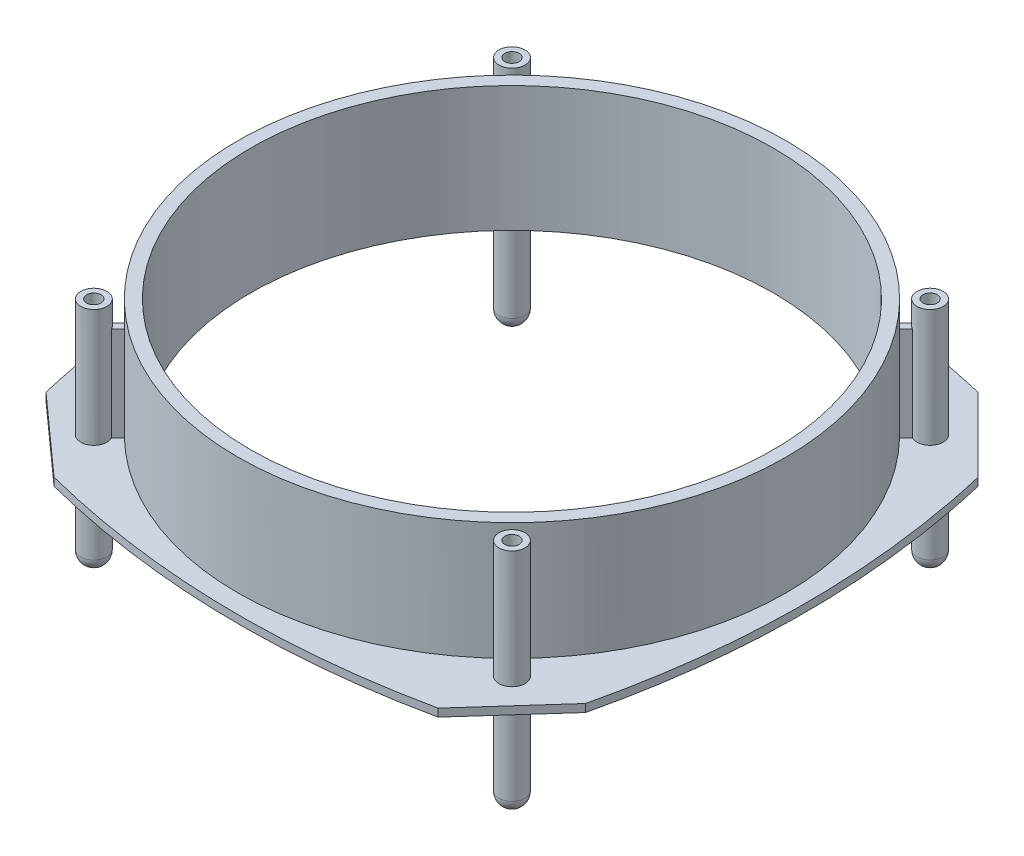
SolidWorks part; units mm, degrees
ref_plane "Front Plane" through (0, 0, 0) normal (0, 0, 1) x (1, 0, 0)
ref_plane "Top Plane" through (0, 0, 0) normal (0, 1, 0) x (1, 0, 0)
ref_plane "Right Plane" through (0, 0, 0) normal (1, 0, 0) x (0, 0, -1)
sketch "Sketch2" plane through (0, 0, 0) normal (0, 1, 0) x (1, 0, 0)
  line L0 (3824.4294, -5236.7276) -> (5157.6927, -3749.6242)
  line L2 (5163.9685, 3752.3444) -> (3751.2089, 5164.1439)
  line L4 (-3751.7702, 5163.5828) -> (-5163.7079, 3750.9614)
  line L6 (-5163.0762, -3751.9198) -> (-3675.9728, -5085.183)
  circle A0 centre (0, 0) radius 5000
  spline S0 degree 2 poles (-3751.7702, 5163.5828) (-0.3376, 6037.3855) (3751.2089, 5164.1439) knots 0 0 0 1 1 1
  spline S1 degree 2 poles (-5163.7079, 3750.9614) (-6037.5496, -0.539) (-5163.0762, -3751.9198) knots 0 0 0 1 1 1
  spline S2 degree 2 poles (-3675.9728, -5085.183) (54.6713, -6041.0227) (3824.4294, -5236.7276) knots 0 0 0 1 1 1
  spline S3 degree 2 poles (5163.9685, 3752.3444) (6040.8667, 0.5969) (5157.6927, -3749.6242) knots 0 0 0 1 1 1
extrude "Boss-Extrude2" add sketch "Sketch2" along normal blind 150
sketch "Sketch3" plane through (0, 0, 0) normal (0, 1, 0) x (1, 0, 0)
  circle A0 centre (0, 0) radius 5244.2465
extrude "Boss-Extrude3" add sketch "Sketch3" along normal blind 2400
sketch "Sketch4" plane through (0, 2400, 0) normal (0, 1, 0) x (1, 0, 0)
  circle A0 centre (0, 0) radius 5000
extrude "Cut-Extrude1" cut sketch "Sketch4" against normal blind 3000 contours A0
sketch "Sketch5" plane through (0, 150, 0) normal (0, 1, 0) x (1, 0, 0)
  circle A0 centre (-4000, -4000) radius 250
  circle A1 centre (4000, -4000) radius 250
  circle A2 centre (4000, 4000) radius 250
sketch "Sketch7" plane through (0, 0, 0) normal (0, -1, 0) x (-1, 0, 0)
  circle A0 centre (4000, 4000) radius 250
sketch "Sketch8" plane through (0, 150, 0) normal (0, 1, 0) x (1, 0, 0)
  line L0 (3785.2923, -3871.9351) -> (3569.5398, -3651.2442)
  circle A0 centre (4000, -4000) radius 250 construction
  point P0 (3786.5537, -3873.2254)
  point P4 (3786.5537, -3873.2254)
  point P5 (3786.5537, -3873.2254)
  point P6 (3888.8138, -3773.2537)
  point P11 (3890.7516, -3775.1339)
extrude "Extrude-Thin9" [suppressed] add sketch "Sketch8" along normal blind 2400 thin thin type one direction wall 128
extrude "Boss-Extrude11" [suppressed] add sketch "Sketch5" along normal blind 2850 and the other way blind 1900 contours A1
sketch "Sketch9" plane through (0, 0, 0) normal (0, -1, 0) x (-1, 0, 0)
  circle A0 centre (4000, 4000) radius 250
extrude "Boss-Extrude12" add sketch "Sketch7" against normal blind 2400 contours A0
extrude "Boss-Extrude13" add sketch "Sketch9" along normal blind 2000 contours A0
fillet "Fillet1" radius 250 2 edges at (-4000, 0, -4250) (-4000, -2000, -4250)
sketch "Sketch10" plane through (0, 2400, 0) normal (0, 1, 0) x (1, 0, 0)
  circle A0 centre (-4000, 4000) radius 137.4456
extrude "Cut-Extrude2" cut sketch "Sketch10" against normal blind 500
sketch "Sketch13" plane through (0, 150, 0) normal (0, 1, 0) x (1, 0, 0)
  line L0 (-3779.8016, 3881.6249) -> (-3656.9811, 3758.8045)
  line L1 (-3758.8045, 3656.9811) -> (-3881.6249, 3779.8016)
  circle A0 centre (-4000, 4000) radius 250 construction
  circle A1 centre (0, 0) radius 5244.2465 construction
  dimension "D1" = 144
extrude "Extrude-Thin10" add sketch "Sketch13" along normal blind 1800 thin thin type one direction wall 72
ref_axis "Axis1" through (0, 3250, 0) along (0, -1, 0)
pattern_circular "CirPattern1" count 4 over 360 about axis through (0, 3250, 0) along (0, -1, 0) of "Boss-Extrude12", "Boss-Extrude13", "Fillet1", "Cut-Extrude2", "Extrude-Thin10"
scale "Scale2" scale about centroid uniform scaling yes scale factor 0.0315
